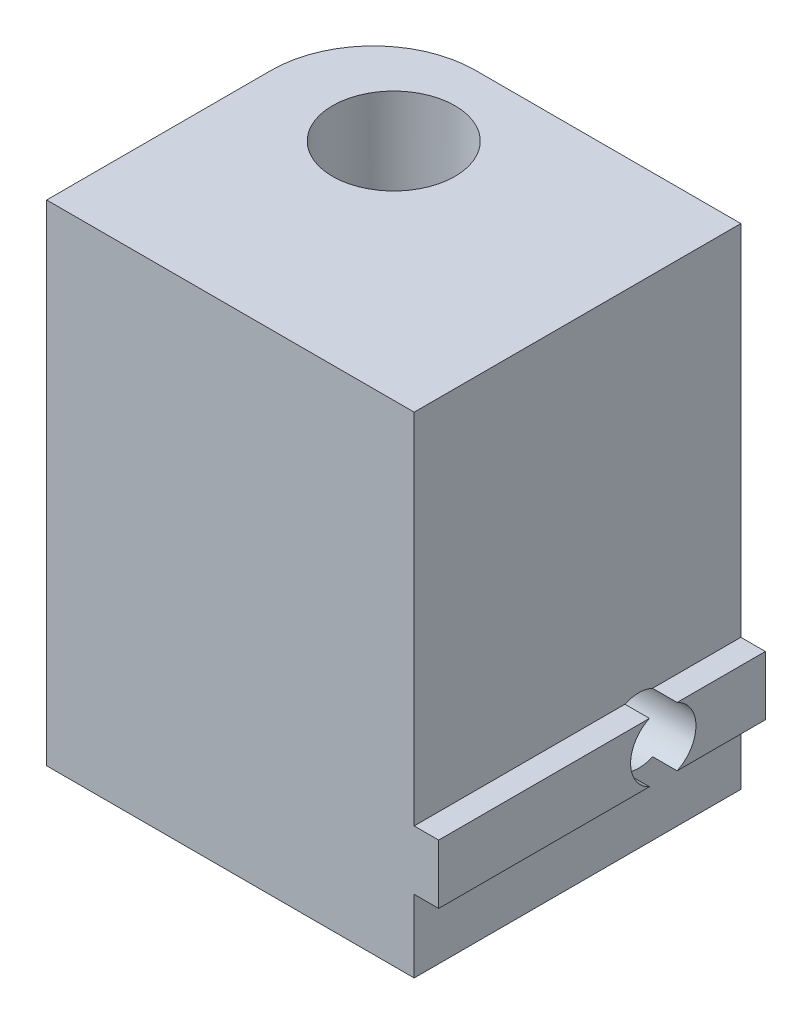
SolidWorks part; units mm, degrees
ref_plane "Front Plane" through (0, 0, 0) normal (0, 0, 1) x (1, 0, 0)
ref_plane "Top Plane" through (0, 0, 0) normal (0, 1, 0) x (1, 0, 0)
ref_plane "Right Plane" through (0, 0, 0) normal (1, 0, 0) x (0, 0, -1)
sketch "Esquisse1" plane through (0, 0, 0) normal (0, 0, 1) x (1, 0, 0)
  line L0 (-9, -5) -> (9, -5)
  line L1 (9, -5) -> (9, -1.45)
  line L2 (9, -1.45) -> (10.2, -1.45)
  line L3 (10.2, -1.45) -> (10.2, 1.45)
  line L4 (10.2, 1.45) -> (9, 1.45)
  line L5 (9, 1.45) -> (9, 19)
  line L6 (9, 19) -> (-9, 19)
  line L7 (-9, 19) -> (-9, -5)
  point P0 (10.2, 0)
  point P11 (0, -5)
  dimension "D1" = 2.9
  dimension "D2" = 1.2
  dimension "D3" = 24
  dimension "D4" = 18
  dimension "D5" = 3.55
extrude "Boss.-Extru.1" add sketch "Esquisse1" along normal blind 16
ref_plane "Plan1" through (6, 0, 0) normal (1, 0, 0) x (0, 0, -1)
sketch "Esquisse2" plane through (6, 0, 0) normal (1, 0, 0) x (0, 0, -1)
  line L0 (0, 1.45) -> (0, 19) construction
  line L1 (-12, 14) -> (0, 14)
  line L2 (-12, 14) -> (-12, 5)
  line L3 (-12, 5) -> (0, 5)
  line L4 (0, 14) -> (0, 5)
  line L5 (-16, 19) -> (0, 19) construction
  line L7 (-16, -5) -> (0, -5) construction
  dimension "D1" = 5
  dimension "D2" = 12
  dimension "D3" = 10
extrude "Enlèv. mat.-Extru.1" cut sketch "Esquisse2" against normal through all
sketch "Esquisse3" plane through (0, 0, 0) normal (0, 0, -1) x (-1, 0, 0)
  line L0 (9, 5) -> (-6, 5) construction
  line L1 (9, 5) -> (-6, 5)
  line L2 (9, 5) -> (9, -5)
  line L3 (9, -5) -> (-6, -5)
  line L4 (-6, 5) -> (-6, -5)
  line L5 (9, 5) -> (9, -5) construction
  line L6 (9, -5) -> (-9, -5) construction
  line L7 (-9, 1.45) -> (-9, 19) construction
  dimension "D1" = 3
extrude "Enlèv. mat.-Extru.2" cut sketch "Esquisse3" against normal up to surface (12 mm away) up to face at (-1.5, 9.5, 12)
sketch "Esquisse4" plane through (0, 19, 0) normal (0, 1, 0) x (1, 0, 0)
  line L0 (9, -16) -> (9, 0) construction
  line L1 (9, 0) -> (-9, 0) construction
  circle A0 centre (-3, -5) radius 3
  dimension "D1" = 6
  dimension "D2" = 12
  dimension "D3" = 5
extrude "Enlèv. mat.-Extru.3" cut sketch "Esquisse4" against normal through all and the other way through all
sketch "Esquisse5" plane through (10.2, 0, 0) normal (1, 0, 0) x (0, 0, -1)
  line L0 (0, -1.45) -> (0, 1.45) construction
  circle A0 centre (-5, 0) radius 1.6
  point P4 (0, 0)
  dimension "D1" = 3.2
  dimension "D2" = 5
extrude "MakerBeam Fixing Hole" cut sketch "Esquisse5" against normal through all
fillet "Congé2" radius 5 2 edges at (-9, 16.5, 0) (6, 14, 6)
